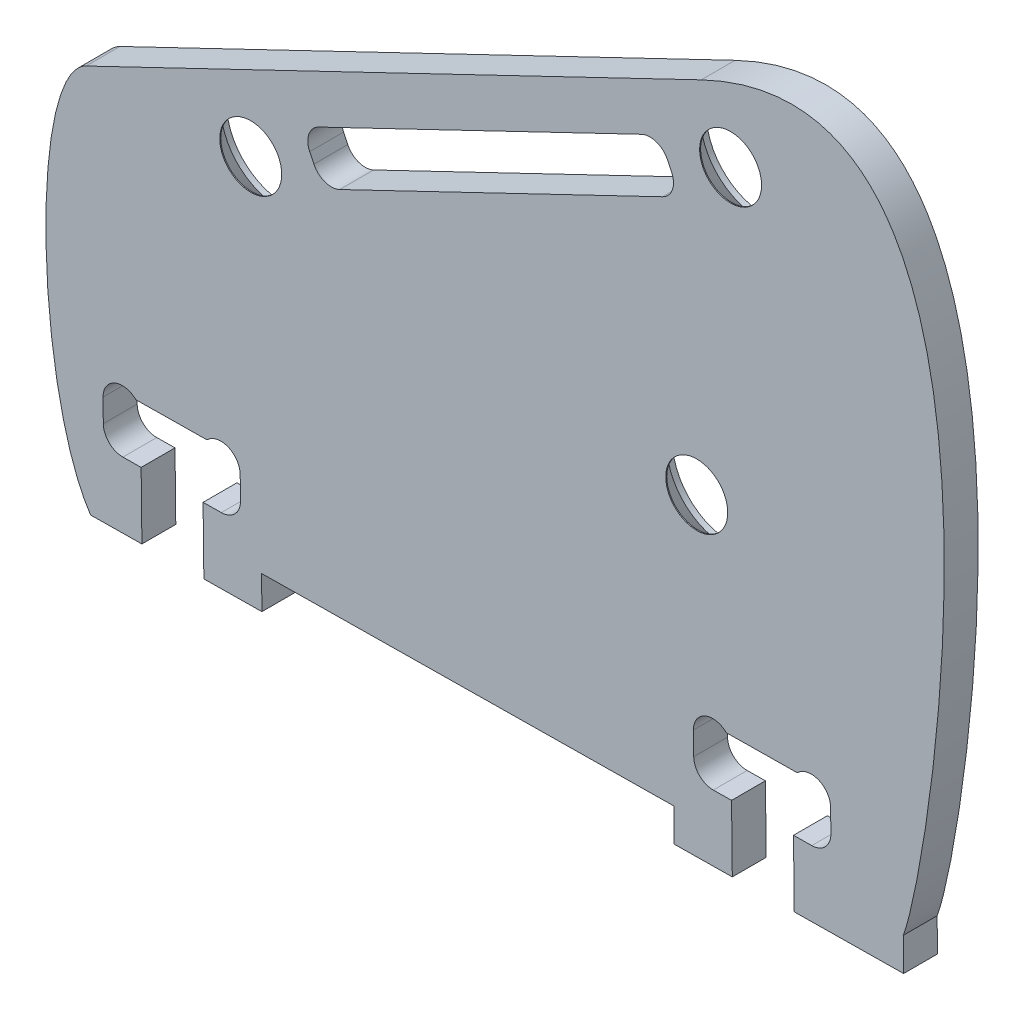
SolidWorks part; units mm, degrees
ref_plane "Front Plane" through (0, 0, 0) normal (0, 0, 1) x (1, 0, 0)
ref_plane "Top Plane" through (0, 0, 0) normal (0, 1, 0) x (1, 0, 0)
ref_plane "Right Plane" through (0, 0, 0) normal (1, 0, 0) x (0, 0, -1)
sketch "Sketch2" plane through (277.9441, -368.7823, 0) normal (0, 0, 1) x (0.9999, 0.0116, 0)
  line L0 (-273.6458, 371.9829) -> (-231.6458, 371.9829)
  line L1 (-237.0451, 403.462) -> (-231.9737, 392.5863)
  line L2 (-273.6458, 390.2567) -> (-231.6458, 390.2567) construction
  line L3 (-269.3958, 375.2829) -> (-238.8958, 375.2829) construction
  line L4 (-238.8958, 373.9829) -> (-238.8958, 371.9829) construction
  line L5 (-241.6964, 405.155) -> (-273.6458, 390.2567)
  line L6 (-273.6458, 390.2567) -> (-273.6458, 371.9829)
  line L7 (-242.1458, 376.5829) -> (-235.6458, 376.5829)
  line L8 (-265.1407, 390.3609) -> (-240.2172, 401.9829) construction
  line L9 (-260.534, 391.1298) -> (-243.7673, 398.9482)
  line L10 (-261.8629, 391.6135) -> (-262.0742, 392.0666)
  line L11 (-243.2836, 400.2771) -> (-243.4949, 400.7303)
  line L12 (-261.5905, 393.3955) -> (-244.8238, 401.214)
  line L13 (-261.4403, 390.7072) -> (-243.9175, 401.6366) construction
  line L14 (-270.1458, 388.0269) -> (-240.2172, 401.9829) construction
  line L15 (-242.861, 399.3708) -> (-262.4968, 392.9729) construction
  line L16 (-254.1458, 375.2829) -> (-254.1458, 371.9829) construction
  line L17 (-242.1458, 376.5829) -> (-242.1458, 373.9829)
  line L18 (-242.1458, 373.9829) -> (-235.6458, 373.9829)
  line L19 (-235.6458, 376.5829) -> (-235.6458, 373.9829)
  line L20 (-242.1458, 376.5829) -> (-235.6458, 373.9829) construction
  line L21 (-242.1458, 373.9829) -> (-235.6458, 376.5829) construction
  line L22 (-242.1458, 376.5829) -> (-239.5458, 373.9829) construction
  line L23 (-240.4958, 371.9829) -> (-237.2958, 371.9829)
  line L24 (-240.4958, 371.9829) -> (-240.4958, 373.9829)
  line L25 (-240.4958, 373.9829) -> (-237.2958, 373.9829)
  line L26 (-237.2958, 371.9829) -> (-237.2958, 373.9829)
  line L27 (-240.4958, 371.9829) -> (-237.2958, 373.9829) construction
  line L28 (-240.4958, 373.9829) -> (-237.2958, 371.9829) construction
  line L29 (-238.8958, 376.5829) -> (-238.8958, 373.9829) construction
  line L30 (-242.4387, 374.69) -> (-242.4387, 375.8758)
  line L31 (-235.3529, 375.8758) -> (-235.3529, 374.69)
  line L32 (-267.7958, 371.9829) -> (-267.7958, 373.9829)
  line L33 (-270.9958, 371.9829) -> (-270.9958, 373.9829)
  line L34 (-266.1458, 373.9829) -> (-272.6458, 373.9829)
  line L35 (-272.9387, 375.8758) -> (-272.9387, 374.69)
  line L36 (-266.1458, 376.5829) -> (-272.6458, 376.5829)
  line L37 (-265.8529, 374.69) -> (-265.8529, 375.8758)
  line L38 (-241.4387, 373.69) -> (-236.3529, 373.69)
  line L39 (-231.6458, 391.1072) -> (-231.6458, 371.9829)
  line L40 (-266.8529, 373.69) -> (-271.9387, 373.69)
  line L42 (-270.9958, 371.9829) -> (-273.6458, 371.9829)
  line L43 (-270.9958, 371.9829) -> (-270.9958, 370.2829)
  line L44 (-270.9958, 370.2829) -> (-273.6458, 370.2829)
  line L45 (-273.6458, 371.9829) -> (-273.6458, 370.2829)
  line L46 (-231.6458, 371.9829) -> (-237.2958, 371.9829)
  line L47 (-231.6458, 371.9829) -> (-231.6458, 370.2829)
  line L48 (-231.6458, 370.2829) -> (-237.2958, 370.2829)
  line L49 (-237.2958, 371.9829) -> (-237.2958, 370.2829)
  line L50 (-267.7958, 371.9829) -> (-264.7958, 371.9829)
  line L51 (-267.7958, 371.9829) -> (-267.7958, 370.2829)
  line L52 (-267.7958, 370.2829) -> (-264.7958, 370.2829)
  line L53 (-264.7958, 371.9829) -> (-264.7958, 370.2829)
  line L54 (-240.4958, 371.9829) -> (-243.4958, 371.9829)
  line L55 (-240.4958, 371.9829) -> (-240.4958, 370.2829)
  line L56 (-240.4958, 370.2829) -> (-243.4958, 370.2829)
  line L57 (-243.4958, 371.9829) -> (-243.4958, 370.2829)
  circle A0 centre (-242.1458, 386.4829) radius 1.6
  circle A1 centre (-265.1407, 390.3609) radius 1.6
  circle A2 centre (-240.2172, 401.9829) radius 1.6
  circle A3 centre (-270.1458, 388.0269) radius 3.5
  circle A4 centre (-240.2172, 401.9829) radius 3.5
  arc A5 (-262.0742, 392.0666) -> (-261.5905, 393.3955) centre (-261.1679, 392.4892) cw
  circle A6 centre (-235.1458, 391.1072) radius 3.5
  circle A7 centre (-241.4387, 375.8758) radius 1
  circle A8 centre (-236.3529, 375.8758) radius 1
  circle A9 centre (-236.3529, 374.69) radius 1
  circle A10 centre (-241.4387, 374.69) radius 1
  arc A11 (-261.8629, 391.6135) -> (-260.534, 391.1298) centre (-260.9566, 392.0361) ccw
  arc A12 (-243.7673, 398.9482) -> (-243.2836, 400.2771) centre (-244.1899, 399.8545) ccw
  circle A13 centre (-271.9387, 374.69) radius 1
  circle A14 centre (-271.9387, 375.8758) radius 1
  circle A15 centre (-266.8529, 375.8758) radius 1
  circle A16 centre (-266.8529, 374.69) radius 1
  arc A17 (-243.4949, 400.7303) -> (-244.8238, 401.214) centre (-244.4012, 400.3077) ccw
  spline S0 degree 3 poles (-273.6458, 370.2829) (-276.3858, 374.3745) (-276.7083, 388.8286) (-273.6458, 390.2567) knots 0 0 0 0 1 1 1 1
  spline S1 degree 3 poles (-241.6964, 405.155) (-223.9419, 413.434) (-230.011, 376.1612) (-231.6458, 371.9829) knots 0 0 0 0 1 1 1 1
  point P10 (-252.6789, 396.1719)
  point P15 (-240.2172, 401.9829)
  point P21 (-238.8958, 372.9829)
  dimension "D1" = 3.2
  dimension "D10" = 3.2
  dimension "D13" = 20.5
  dimension "D2" = 7
  dimension "D17" = 1
  dimension "D11" = 45
  dimension "D14" = 2
  dimension "D3" = 30
  dimension "D4" = 12
  dimension "D5" = 30.5
  dimension "D6" = 4.25
  dimension "D7" = 6.5
  dimension "D8" = 2.6
  dimension "D9" = 2
  dimension "D12" = 2.5
  dimension "D15" = 25
  dimension "D16" = 14.5
  dimension "D18" = 12
  dimension "D19" = 42
  dimension "D20" = 1.7
  dimension "D21" = 3
extrude "Boss-Extrude1" add sketch "Sketch2" along normal blind 1.75 contours A17 L11 A4 L5 A3 L6 L0 L39 A6 L1 A12 L9 A11 L10 A5 L12 A1 A0 | A3 | A6 | A4 A2 | S0 L45 L6 | A3 L5 L6 | S1 A4 L1 A6 L39 | L0 L45 L44 L43 | L53 L0 L51 L52 | L0 L57 L56 L55 | L0 L49 L48 L47 region at (22.3547, 12.8494, 0) region at (-1.0114, 8.8009, 0) region at (1.3348, -0.8346, 0) region at (40.9915, 23.0224, 0) region at (0.2187, 18.0051, 0) region at (3.3136, 16.0836, 0) region at (7.3594, -0.7646, 0) region at (34.2042, 33.5951, 0) region at (31.6577, -0.4827, 0) region at (39.1822, -0.3953, 0) region at (38.2755, 19.5698, 0)
sketch "Sketch3" plane through (0, 0, 1.75) normal (0, 0, 1) x (1, 0, 0)
  circle A0 centre (8.2913, 18.4755) radius 3
  circle A1 centre (31.3296, 14.8646) radius 3
  circle A2 centre (33.0782, 30.3859) radius 3
  dimension "D1" = 6
extrude "Cut-Extrude2" [suppressed] cut sketch "Sketch3" against normal blind 0.3
chamfer "Chamfer1" [suppressed] distance 1.4 angle 45
sketch "Sketch4" plane through (0, 0, 0) normal (0, 0, -1) x (-1, 0, 0)
  circle A0 centre (-33.0782, 30.3859) radius 3
  circle A1 centre (-8.2913, 18.4755) radius 3
  circle A2 centre (-31.3296, 14.8646) radius 3
  dimension "D1" = 6
extrude "Cut-Extrude3" cut sketch "Sketch4" against normal blind 0.3
chamfer "Chamfer2" distance 1.4 angle 45 3 edges at (29.7296, 14.8646, 0.3) (6.6913, 18.4755, 0.3) (31.4782, 30.3859, 0.3)
